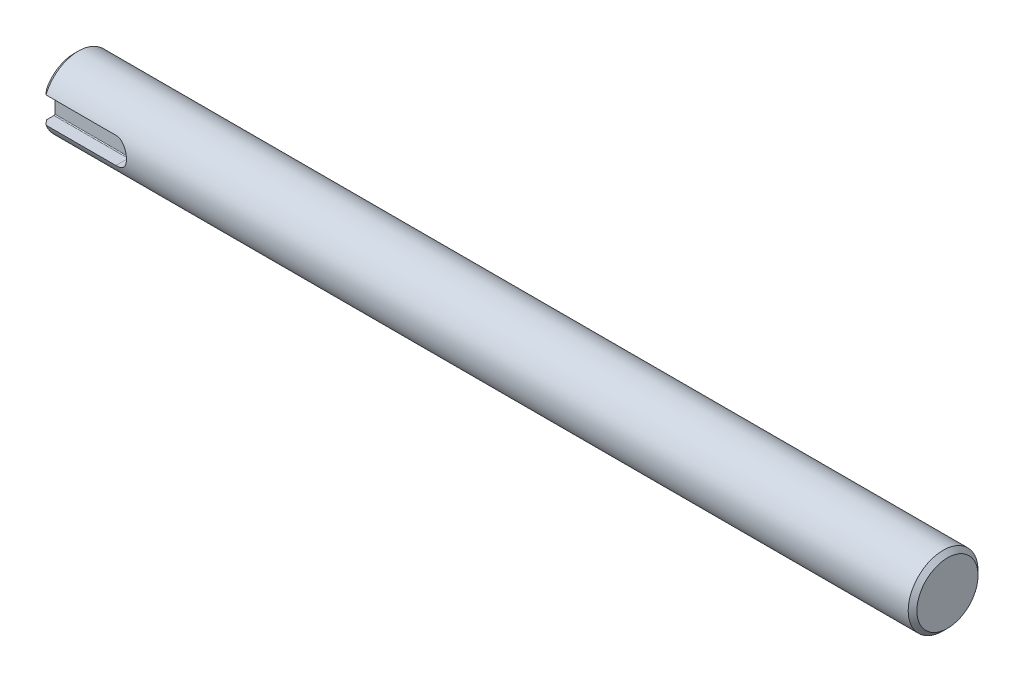
SolidWorks part; units mm, degrees
ref_plane "Front Plane" through (0, 0, 0) normal (0, 0, 1) x (1, 0, 0)
ref_plane "Top Plane" through (0, 0, 0) normal (0, 1, 0) x (1, 0, 0)
ref_plane "Right Plane" through (0, 0, 0) normal (1, 0, 0) x (0, 0, -1)
sketch "Sketch1" plane through (0, 0, 0) normal (0, 0, 1) x (1, 0, 0)
  line L0 (0, 0) -> (100, 0) construction
  line L1 (0, 0) -> (100, 0)
  line L2 (100, 0) -> (100, 4)
  line L3 (100, 4) -> (0, 4)
  line L4 (0, 4) -> (0, 0)
  dimension "L" = 100
  dimension "D" = 8
revolve "Revolve1" add sketch "Sketch1" angle 360 about L0
chamfer "Chamfer1" distance 0.5 angle 45 2 edges at (100, 0, 4) (0, 0, 4)
ref_plane "Plane1" through (0, 0, 4) normal (0, 0, 1) x (1, 0, 0)
ref_plane "Plane2" through (100, 0, 0) normal (1, 0, 0) x (0, 0, -1)
other "DeleteFace1" [suppressed]
chamfer "Chamfer2" [suppressed] distance 2 angle 45
ref_plane "Dim. KC" through (0, 0, 0) normal (1, 0, 0) x (0, 0, -1)
ref_plane "Plane3" through (0, 0, 0) normal (1, 0, 0) x (0, 0, -1)
ref_plane "Plane4" through (10, 0, 0) normal (1, 0, 0) x (0, 0, -1)
sketch "Sketch2" plane through (0, 0, 4) normal (0, 0, 1) x (1, 0, 0)
  line L0 (0, 0) -> (10, 0) construction
  line L1 (0, 1.5) -> (10, 1.5)
  line L2 (0, 1.5) -> (0, -1.5) construction
  line L3 (0, -1.5) -> (10, -1.5)
  line L4 (10, 1.5) -> (10, -1.5) construction
  line L5 (5, 1.5) -> (5, -1.5) construction
  line L6 (0, -4.4) -> (0, 4.4) construction
  line L7 (10, 1.5) -> (10, -1.5)
  line L8 (10, -4.4) -> (10, 4.4) construction
  line L9 (0, 1.5) -> (0, -1.5)
  line L12 (0, -4.4) -> (0, 4.4) construction
  dimension "A" = 10
  dimension "B_s" = 3
extrude "Boss-Extrude1" add sketch "Sketch2" against normal blind 1.8 separate body
fillet "Fillet1" [suppressed] type full round
fillet "Fillet2" 2 edges at (10, 1.5, 3.1) (10, -1.5, 3.1) type full round first side face at (5, 1.5, 3.1) second side face at (5, -1.5, 3.1) middle face at (10, 0, 3.1)
sketch "Sketch3" plane through (0, 0, 4) normal (0, 0, 1) x (1, 0, 0)
  line L0 (11, 1.5) -> (11, -1.5) construction
  line L1 (8.5, 1.5) -> (13.5, 1.5)
  line L2 (8.5, 1.5) -> (8.5, -1.5)
  line L3 (8.5, -1.5) -> (13.5, -1.5)
  line L4 (13.5, 1.5) -> (13.5, -1.5)
  line L7 (8.5, 0) -> (13.5, 0) construction
  line L9 (12, 1.5) -> (12, -1.5) construction
  line L10 (10, 1.5) -> (10, -1.5) construction
  line L11 (0, 1.5) -> (10, 1.5) construction
  line L12 (0, -1.5) -> (10, -1.5) construction
  dimension "D1" = 1.5
  dimension "D2" = 2
  dimension "D3" = 1.5
extrude "Boss-Extrude2" [suppressed] add sketch "Sketch3" against normal blind 1.8
fillet "Fillet3" radius 0.1 4 edges at (4.25, -1.5, 2.2) (10, 0, 2.2) (4.25, 1.5, 2.2) (0, 0, 2.2)
other "DeleteFace2" face at (0.0396, 0, 2.2396) and patch yes
other "DeleteFace3" [suppressed]
combine bodies "Combine1" operation type subtract main body 101 bodies to subtract 136
ref_plane "KC_SEC1" through (5, 0, 0) normal (1, 0, 0) x (0, 0, -1)
ref_plane "KC_SEC2" through (11, 0, 0) normal (1, 0, 0) x (0, 0, -1)
ref_plane "Dim. WKC" [suppressed] through (2, 0, 0) normal (1, 0, 0) x (0, 0, -1)
ref_plane "Dim. K" [suppressed] through (20, 0, 0) normal (1, 0, 0) x (0, 0, -1)
ref_plane "Plane5" [suppressed] through (2, 0, 0) normal (1, 0, 0) x (0, 0, -1)
ref_plane "Plane6" [suppressed] through (20, 0, 0) normal (1, 0, 0) x (0, 0, -1)
sketch "Sketch4" [suppressed] plane through (0, 0, 4) normal (0, 0, 1) x (1, 0, 0)
  line L0 (2, 1.5) -> (2, -1.5)
  line L1 (2, 1.5) -> (8, 1.5)
  line L2 (2, 1.5) -> (2, -1.5) construction
  line L3 (2, -1.5) -> (8, -1.5)
  line L4 (8, 1.5) -> (8, -1.5)
  line L5 (2, -4.4) -> (2, 4.4) construction
  line L6 (2, -3.3) -> (2, 3.3) construction
  line L7 (8, 0) -> (2, 0) construction
  line L8 (5, 1.5) -> (5, -1.5) construction
  dimension "B_s" = 3
  dimension "C" = 6
extrude "Boss-Extrude3" [suppressed] add sketch "Sketch4" against normal blind 1.8 separate body
sketch "Sketch5" [suppressed] plane through (0, 0, 4) normal (0, 0, 1) x (1, 0, 0)
  line L0 (0, 0) -> (20, 0) construction
  line L2 (20, -3.3) -> (20, 3.3) construction
  line L4 (20, -3.3) -> (20, 3.3) construction
  line L5 (17, 1.5) -> (17, -1.5) construction
  line L9 (14, 1.5) -> (20, 1.5)
  line L10 (14, 1.5) -> (14, -1.5)
  line L11 (14, -1.5) -> (20, -1.5)
  line L12 (20, 1.5) -> (20, -1.5) construction
  line L13 (20, 1.5) -> (20, -1.5)
  dimension "B_s" = 3
  dimension "E" = 6
extrude "Boss-Extrude4" [suppressed] add sketch "Sketch5" against normal blind 1.8 separate body
sketch "Sketch6" [suppressed] plane through (0, 0, 4) normal (0, 0, 1) x (1, 0, 0)
  line L0 (2, 1.5) -> (8, 1.5) construction
  line L1 (6.5, 1.5) -> (11.5, 1.5)
  line L2 (6.5, 1.5) -> (6.5, -1.5)
  line L3 (6.5, -1.5) -> (11.5, -1.5)
  line L4 (11.5, 1.5) -> (11.5, -1.5)
  line L5 (2, -1.5) -> (8, -1.5) construction
  line L6 (8, 1.5) -> (8, -1.5) construction
  line L7 (9, 1.5) -> (9, -1.5) construction
  line L8 (10, 1.5) -> (10, -1.5) construction
  dimension "D1" = 1.5
  dimension "D2" = 2
  dimension "D3" = 1.5
extrude "Boss-Extrude5" [suppressed] add sketch "Sketch6" against normal blind 1.8
fillet "Fillet4" [suppressed] type full round
fillet "Fillet5" [suppressed] type full round
fillet "Fillet6" [suppressed] radius 0.1
fillet "Fillet7" [suppressed] type full round
fillet "Fillet8" [suppressed] type full round
fillet "Fillet9" [suppressed] radius 0.1
other "DeleteFace4" [suppressed]
other "DeleteFace5" [suppressed]
other "DeleteFace6" [suppressed]
other "DeleteFace7" [suppressed]
combine bodies "Combine2" [suppressed] operation type subtract main body 101 bodies to subtract 149 135
ref_plane "WKC_SEC1" [suppressed] through (5, 0, 0) normal (1, 0, 0) x (0, 0, -1)
ref_plane "WKC_SEC2" [suppressed] through (17, 0, 0) normal (1, 0, 0) x (0, 0, -1)
ref_plane "WKC_SEC3" [suppressed] through (9, 0, 0) normal (1, 0, 0) x (0, 0, -1)
ref_plane "Dim. KZ" [suppressed] through (2, 0, 0) normal (1, 0, 0) x (0, 0, -1)
ref_plane "Plane7" [suppressed] through (2, 0, 0) normal (1, 0, 0) x (0, 0, -1)
ref_plane "Plane8" [suppressed] through (8, 0, 0) normal (1, 0, 0) x (0, 0, -1)
sketch "Sketch7" [suppressed] plane through (0, 0, 4) normal (0, 0, 1) x (1, 0, 0)
  line L0 (0, 0) -> (8, 0) construction
  line L1 (2, 1.5) -> (8, 1.5)
  line L2 (2, 1.5) -> (2, -1.5) construction
  line L3 (2, -1.5) -> (8, -1.5)
  line L4 (8, 1.5) -> (8, -1.5) construction
  line L5 (2, -4.4) -> (2, 4.4) construction
  line L6 (2, -4.4) -> (2, 4.4) construction
  line L7 (2, 1.5) -> (2, -1.5)
  line L8 (8, 1.5) -> (8, -1.5)
  line L9 (8, -4.4) -> (8, 4.4) construction
  line L10 (5, 1.5) -> (5, -1.5) construction
  dimension "B_s" = 3
  dimension "Z" = 6
extrude "Boss-Extrude6" [suppressed] add sketch "Sketch7" against normal blind 1.8 separate body
fillet "Fillet10" [suppressed] type full round
fillet "Fillet11" [suppressed] type full round
sketch "Sketch8" [suppressed] plane through (0, 0, 4) normal (0, 0, 1) x (1, 0, 0)
  line L0 (1, 1.5) -> (1, -1.5) construction
  line L1 (-1.5, 1.5) -> (3.5, 1.5)
  line L2 (-1.5, 1.5) -> (-1.5, -1.5)
  line L3 (-1.5, -1.5) -> (3.5, -1.5)
  line L4 (3.5, 1.5) -> (3.5, -1.5)
  line L5 (2, 1.5) -> (2, -1.5) construction
  line L7 (-1.5, 0) -> (3.5, 0) construction
  line L9 (0, 1.5) -> (0, -1.5) construction
  line L10 (2, 1.5) -> (8, 1.5) construction
  line L11 (2, -1.5) -> (8, -1.5) construction
  dimension "D1" = 1.5
  dimension "D2" = 2
  dimension "D3" = 1.5
extrude "Boss-Extrude7" [suppressed] add sketch "Sketch8" against normal blind 1.8
fillet "Fillet12" [suppressed] radius 0.1
other "DeleteFace8" [suppressed]
other "DeleteFace9" [suppressed]
combine bodies "Combine3" [suppressed] operation type subtract main body 101 bodies to subtract 147
ref_plane "KZ_SEC1" [suppressed] through (5, 0, 0) normal (1, 0, 0) x (0, 0, -1)
ref_plane "KZ_SEC2" [suppressed] through (1, 0, 0) normal (1, 0, 0) x (0, 0, -1)
ref_plane "Dim. FC" [suppressed] through (1, 0, 0) normal (1, 0, 0) x (0, 0, -1)
sketch "Sketch9" [suppressed] plane through (0, 0, 0) normal (0, 1, 0) x (1, 0, 0)
  line L0 (0, 0) -> (2, 0) construction
  line L1 (1, -3) -> (2, -3)
  line L2 (1, -3) -> (1, -4)
  line L3 (1, -4) -> (2, -4)
  line L4 (2, -3) -> (2, -4)
  line L5 (1, -3.3) -> (1, 3.3) construction
  line L6 (1.5, -4) -> (1.5, -3) construction
  dimension "G" = 1
  dimension "H" = 1
  dimension "D" = 8
extrude "Cut-Extrude1" [suppressed] cut sketch "Sketch9" against normal through all and the other way through all
ref_plane "FC_SEC" [suppressed] through (1.5, 0, 0) normal (1, 0, 0) x (0, 0, -1)
ref_plane "Dim. WFC" [suppressed] through (1, 0, 0) normal (1, 0, 0) x (0, 0, -1)
ref_plane "Dim. W" [suppressed] through (19, 0, 0) normal (1, 0, 0) x (0, 0, -1)
sketch "Sketch10" [suppressed] plane through (0, 0, 0) normal (0, 1, 0) x (1, 0, 0)
  line L0 (0, 0) -> (19, 0) construction
  line L1 (1, -4) -> (2, -4)
  line L2 (1, -4) -> (1, -3)
  line L3 (1, -3) -> (2, -3)
  line L4 (2, -4) -> (2, -3)
  line L5 (1.5, -3) -> (1.5, -4) construction
  line L6 (19, -4) -> (18, -4)
  line L7 (19, -4) -> (19, -3)
  line L8 (19, -3) -> (18, -3)
  line L9 (18, -4) -> (18, -3)
  line L10 (1, -3.3) -> (1, 3.3) construction
  line L11 (19, -3.3) -> (19, 3.3) construction
  line L12 (18.5, -3) -> (18.5, -4) construction
  dimension "J" = 1
  dimension "V" = 1
  dimension "H" = 1
  dimension "D" = 8
  dimension "H_s_R" = 1
extrude "Cut-Extrude2" [suppressed] cut sketch "Sketch10" against normal through all and the other way through all
ref_plane "WFC_SEC1" [suppressed] through (1.5, 0, 0) normal (1, 0, 0) x (0, 0, -1)
ref_plane "WFC_SEC2" [suppressed] through (18.5, 0, 0) normal (1, 0, 0) x (0, 0, -1)
ref_plane "Dim. SFC" [suppressed] through (1, 0, 0) normal (1, 0, 0) x (0, 0, -1)
sketch "Sketch11" [suppressed] plane through (0, 0, 0) normal (0, 1, 0) x (1, 0, 0)
  line L0 (0, 0) -> (2, 0) construction
  line L1 (1, -4) -> (2, -4)
  line L2 (1, -4) -> (1, -3)
  line L3 (1, -3) -> (2, -3)
  line L4 (2, -4) -> (2, -3)
  line L5 (1, -3.3) -> (1, 3.3) construction
  line L6 (1.5, -3) -> (1.5, -4) construction
  dimension "D" = 8
  dimension "SG" = 1
  dimension "H" = 1
extrude "Cut-Extrude3" [suppressed] cut sketch "Sketch11" against normal through all and the other way through all
pattern_circular "CirPattern1" [suppressed] count 2 every 120 of bodies 119
ref_plane "Plane9" [suppressed] through (0, 0, 0) normal (0, -0.5, 0.866) x (1, 0, 0)
sketch "Sketch12" [suppressed] plane through (0, 0, 0) normal (0, -0.5, 0.866) x (1, 0, 0)
  line L0 (0, 0) -> (2, 0) construction
  line L2 (1, -3) -> (2, -3)
  line L3 (1, -3) -> (1, -4)
  line L4 (1, -4) -> (2, -4)
  line L5 (2, -3) -> (2, -4)
  line L6 (1, -3.3) -> (1, 3.3) construction
  dimension "D" = 8
  dimension "SG" = 1
  dimension "H" = 1
ref_plane "SFC_SEC" [suppressed] through (1.5, 0, 0) normal (1, 0, 0) x (0, 0, -1)
sketch "Sketch13" [suppressed] plane through (1.5, 0, 0) normal (1, 0, 0) x (0, 0, -1)
  line L0 (-4, 0) -> (-3, 0) construction
  line L1 (-3, 0) -> (-4, 0) construction
  line L2 (2, -3.4641) -> (1.5, -2.5981) construction
  line L3 (1.5, -2.5981) -> (2, -3.4641) construction
  line L4 (1.5, -2.5981) -> (2, -3.4641) construction
  dimension "ANG" = 120
sketch "Sketch14" [suppressed] plane through (0, 0, 0) normal (0, 1, 0) x (1, 0, 0)
  line L0 (0, 0) -> (20, 0) construction
  line L1 (1.5, 4) -> (1.5, 3.5) construction
  line L2 (0, 3.5) -> (3, 3.5)
  line L3 (0, 3.5) -> (0, 4)
  line L4 (0, 4) -> (3, 4)
  line L5 (3, 3.5) -> (3, 4)
  line L6 (17, 3.5) -> (20, 3.5)
  line L7 (17, 3.5) -> (17, 4)
  line L8 (17, 4) -> (20, 4)
  line L9 (20, 3.5) -> (20, 4)
  line L10 (0, -4) -> (3, -4)
  line L11 (0, -4) -> (0, -3.5)
  line L12 (0, -3.5) -> (3, -3.5)
  line L13 (3, -4) -> (3, -3.5)
  line L14 (17, -4) -> (20, -4)
  line L15 (17, -4) -> (17, -3.5)
  line L16 (17, -3.5) -> (20, -3.5)
  line L17 (20, -4) -> (20, -3.5)
  line L18 (1.5, -3.5) -> (1.5, -4) construction
  line L19 (18.5, 4) -> (18.5, 3.5) construction
  line L20 (18.5, -3.5) -> (18.5, -4) construction
  dimension "D" = 8
  dimension "W_1" = 7
  dimension "KWC" = 3
  dimension "KWC_L1" = 3
  dimension "KWC_R1" = 3
  dimension "KWC_R2" = 3
  dimension "W_1_R" = 7
extrude "Cut-Extrude4" [suppressed] cut sketch "Sketch14" against normal through all and the other way through all
ref_plane "KWC_SEC1" [suppressed] through (1.5, 0, 0) normal (1, 0, 0) x (0, 0, -1)
ref_plane "KWC_SEC2" [suppressed] through (18.5, 0, 0) normal (1, 0, 0) x (0, 0, -1)
sketch "Sketch15" [suppressed] plane through (0, 0, 0) normal (0, 1, 0) x (1, 0, 0)
  line L0 (0, 0) -> (20, 0) construction
  line L1 (1.5, -3) -> (1.5, -4) construction
  line L2 (0, 3) -> (3, 3)
  line L3 (0, 3) -> (0, 4)
  line L4 (0, 4) -> (3, 4)
  line L5 (3, 3) -> (3, 4)
  line L6 (17, 3) -> (20, 3)
  line L7 (17, 3) -> (17, 4)
  line L8 (17, 4) -> (20, 4)
  line L9 (20, 3) -> (20, 4)
  line L10 (0, -4) -> (3, -4)
  line L11 (0, -4) -> (0, -3)
  line L12 (0, -3) -> (3, -3)
  line L13 (3, -4) -> (3, -3)
  line L14 (17, -4) -> (20, -4)
  line L15 (17, -4) -> (17, -3)
  line L16 (17, -3) -> (20, -3)
  line L17 (20, -4) -> (20, -3)
  line L18 (18.5, -3) -> (18.5, -4) construction
  dimension "D" = 8
  dimension "KWC_L1" = 3
  dimension "KWC_R1" = 3
  dimension "WC" = 6
  dimension "KWC" = 3
  dimension "KWC_R2" = 3
  dimension "WC_R" = 6
extrude "Cut-Extrude5" [suppressed] cut sketch "Sketch15" against normal through all and the other way through all
ref_plane "WC_SEC1" [suppressed] through (1.5, 0, 0) normal (1, 0, 0) x (0, 0, -1)
ref_plane "WC_SEC2" [suppressed] through (18.5, 0, 0) normal (1, 0, 0) x (0, 0, -1)
sketch "Sketch16" [suppressed] plane through (0, 0, 0) normal (0, 0, 1) x (1, 0, 0)
  line L0 (20, 4) -> (0, 4) construction
  line L1 (1.1, 3.5) -> (2, 3.5)
  line L2 (1.1, 3.5) -> (1.1, 4)
  line L3 (1.1, 4) -> (2, 4)
  line L4 (2, 3.5) -> (2, 4)
  line L5 (0, 0) -> (2, 0) construction
  line L6 (0, 4) -> (0, 0) construction
  dimension "D_s_1" = 7
  dimension "M_s" = 0.9
  dimension "TA" = 2
revolve "Cut-Revolve1" [suppressed] cut sketch "Sketch16" angle 360 about L5
sketch "Sketch17" [suppressed] plane through (0, 0, 0) normal (0, 0, 1) x (1, 0, 0)
  line L1 (18, 3.5) -> (18.9, 3.5)
  line L2 (18, 3.5) -> (18, 4)
  line L3 (18, 4) -> (18.9, 4)
  line L4 (18.9, 3.5) -> (18.9, 4)
  line L5 (0, 0) -> (20, 0) construction
  line L7 (20, -3.3) -> (20, 3.3) construction
  dimension "D_s_1" = 7
  dimension "M_s" = 0.9
  dimension "D" = 8
  dimension "TB" = 2
revolve "Cut-Revolve2" [suppressed] cut sketch "Sketch17" angle 360 about L5
sketch "Sketch18" [suppressed] plane through (0, 0, 0) normal (0, 0, 1) x (1, 0, 0)
  line L0 (0, 0) -> (20, 0) construction
  line L1 (0, 4) -> (0, -4) construction
  line L3 (1, 4) -> (5, 4)
  line L4 (1, 4) -> (1, 3.5)
  line L5 (1, 3.5) -> (5, 3.5)
  line L6 (5, 4) -> (5, 3.5)
  line L7 (20, 4) -> (0, 4) construction
  line L8 (20, -3.3) -> (20, 3.3) construction
  dimension "D_s_2" = 7
  dimension "UC" = 1
  dimension "L1_s" = 4
revolve "Cut-Revolve3" [suppressed] cut sketch "Sketch18" angle 360 about L0
ref_plane "Dim. SC" [suppressed] through (2, 0, 0) normal (1, 0, 0) x (0, 0, -1)
sketch "Sketch19" [suppressed] plane through (0, 0, 0) normal (0, 1, 0) x (1, 0, 0)
  line L0 (20, -3.3) -> (20, 3.3) construction
  line L1 (2, -3.5) -> (10, -3.5)
  line L2 (2, -3.5) -> (2, -4)
  line L3 (2, -4) -> (10, -4)
  line L4 (10, -3.5) -> (10, -4)
  line L5 (2, 4) -> (10, 4)
  line L6 (2, 4) -> (2, 3.5)
  line L7 (2, 3.5) -> (10, 3.5)
  line L8 (10, 4) -> (10, 3.5)
  line L9 (6, 4) -> (6, 3.5) construction
  line L10 (6, -3.5) -> (6, -4) construction
  line L12 (0, 0) -> (20, 0) construction
  line L14 (2, -3.3) -> (2, 3.3) construction
  dimension "W_2" = 7
  dimension "L2_s" = 8
  dimension "D" = 8
  dimension "L2_s_L1" = 8
extrude "Cut-Extrude6" [suppressed] cut sketch "Sketch19" against normal through all and the other way through all
ref_plane "SC_SEC" [suppressed] through (6, 0, 0) normal (1, 0, 0) x (0, 0, -1)
equation "\"Plane dim\"= \"D@Sketch1\" * 0.5"
equation "\"D1@Plane3\"= if ( \"KC@Dim. KC\" < 1 , 0 , \"KC@Dim. KC\" )"
equation "\"D1@Plane4\" = if ( \"KC@Dim. KC\" > \"L@Sketch1\" - \"A@Sketch2\" - 1 , \"L@Sketch1\" , \"KC@Dim. KC\" + \"A@Sketch2\" )"
equation "\"D1@Plane5\"=if ( \"WKC@Dim. WKC\" < 1 , 0 , \"WKC@Dim. WKC\" )"
equation "\"D1@Plane6\"=if ( \"K@Dim. K\" < 1 , 0 , \"K@Dim. K\" )"
equation "\"D1@Plane7\"=if ( \"KZ@Dim. KZ\" < 1 , 0 , \"KZ@Dim. KZ\" )"
equation "\"D1@Plane8\"=if ( \"KZ@Dim. KZ\" > \"L@Sketch1\" - \"Z@Sketch7\" - 1 , \"L@Sketch1\", \"KZ@Dim. KZ\" + \"Z@Sketch7\" )"
equation "\"D1@Sketch3\"=\"B_s@Sketch2\"/2"
equation "\"D3@Sketch3\"=\"B_s@Sketch2\"/2"
equation "\"D1@Sketch8\"=\"B_s@Sketch7\"/2"
equation "\"D3@Sketch8\"=\"B_s@Sketch7\"/2"
equation "\"D1@Sketch6\"=\"B_s@Sketch4\"/2"
equation "\"D3@Sketch6\"=\"B_s@Sketch4\"/2"
equation "\"D@Sketch12\" = \"D@Sketch11\""
equation "\"SG@Sketch12\" = \"SG@Sketch11\""
equation "\"H@Sketch12\"= \"H@Sketch11\""
